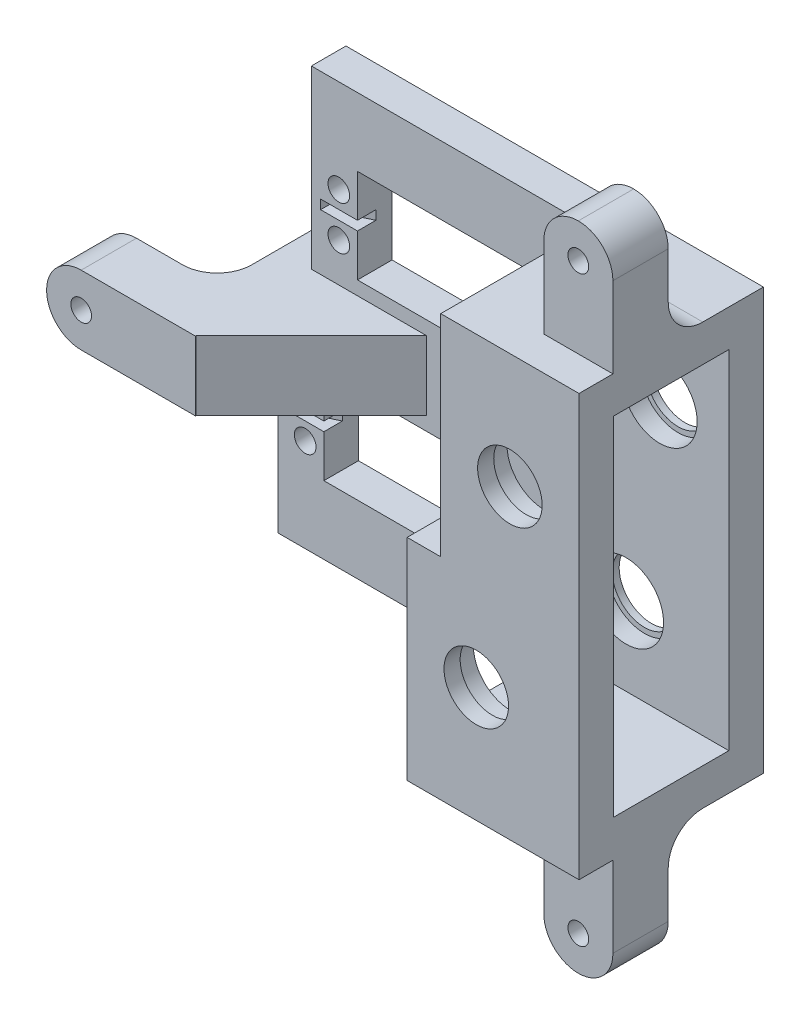
SolidWorks part; units mm, degrees
ref_plane "Front Plane" through (0, 0, 0) normal (0, 0, 1) x (1, 0, 0)
ref_plane "Top Plane" through (0, 0, 0) normal (0, 1, 0) x (1, 0, 0)
ref_plane "Right Plane" through (0, 0, 0) normal (1, 0, 0) x (0, 0, -1)
sketch "Sketch1" plane through (0, 0, 0) normal (0, 0, 1) x (1, 0, 0)
  line L0 (-15, 0) -> (22.2932, 0)
  line L5 (-15, 91.3619) -> (22.2932, 91.3619)
  line L6 (-15, 0) -> (-15, 91.3619)
  line L7 (22.2932, 0) -> (22.2932, 91.3619)
  line L8 (0, 25) -> (7.2932, 66.3619) construction
  line L9 (0, 25) -> (0, 79.2) construction
  circle A1 centre (0, 25) radius 8.125
  circle A2 centre (7.2932, 66.3619) radius 8.125
  point P4 (0, 0)
  dimension "D2" = 16.25
  dimension "D5" = 25
  dimension "D4" = 15
  dimension "D6" = 25
  dimension "D8" = 42
  dimension "D9" = 10
  dimension "D10" = 15
extrude "Boss-Extrude1" add sketch "Sketch1" along normal blind 40
ref_plane "INNER WALL" through (0, 0, 39) normal (0, 0, 1) x (1, 0, 0)
ref_plane "OUTER WALL" through (0, 0, 32.65) normal (0, 0, 1) x (1, 0, 0)
sketch "Sketch2" plane through (0, 0, 0) normal (0, 1, 0) x (1, 0, 0)
  line L1 (-15, -7.5) -> (22.2932, -7.5)
  line L2 (-15, -7.5) -> (-15, -32.5)
  line L3 (-15, -32.5) -> (22.2932, -32.5)
  line L4 (22.2932, -7.5) -> (22.2932, -32.5)
  line L6 (-15, -40) -> (-15, 0) construction
  line L7 (22.2932, -40) -> (22.2932, 0) construction
  point P9 (22.2932, -20)
  point P10 (22.2932, -20)
  dimension "D1" = 25
extrude "Cut-Extrude1" cut sketch "Sketch2" along normal through all from offset 8
sketch "Sketch10" plane through (0, 0, 40) normal (0, 0, 1) x (1, 0, 0)
  circle A0 centre (7.2932, 66.3619) radius 8.125
  circle A1 centre (0, 25) radius 10.837
  circle A2 centre (7.2932, 66.3619) radius 7
  circle A3 centre (0, 25) radius 7
  circle A4 centre (7.2932, 66.3619) radius 8.125 construction
  circle A5 centre (0, 25) radius 8.125 construction
  dimension "D2" = 14
  dimension "D4" = 14
extrude "Boss-Extrude2" add sketch "Sketch10" against normal offset from surface (3.5 mm away) 4 up to face at (-8.125, 25, 32.5)
sketch "Sketch11" plane through (0, 0, 0) normal (0, 0, -1) x (-1, 0, 0)
  circle A0 centre (-7.2932, 66.3619) radius 8.125
  circle A1 centre (-7.2932, 66.3619) radius 7
  circle A2 centre (0, 25) radius 8.125
  circle A3 centre (0, 25) radius 7
  circle A4 centre (0, 25) radius 8.125 construction
  circle A5 centre (-7.2932, 66.3619) radius 8.125 construction
  dimension "D1" = 14
  dimension "D2" = 14
extrude "Boss-Extrude3" add sketch "Sketch11" against normal offset from surface (3.5 mm away) 4 up to face at (8.125, 25, 7.5)
ref_axis "Axis1" through (0, 25, 3.5) along (0, 0, -1)
ref_plane "Plane1" through (0, 25, 0) normal (0, -1, 0) x (-1, 0, 0)
ref_axis "Axis2" through (7.2932, 66.3619, 3.5) along (0, 0, -1)
ref_plane "Plane2" through (0, 66.3619, 0) normal (0, -1, 0) x (-1, 0, 0)
sketch "Sketch12" plane through (0, 0, 0) normal (0, 0, -1) x (-1, 0, 0)
  line L0 (-20.5113, 25) -> (20.5113, 25) construction
  line L1 (15, 0) -> (75.56, 0)
  line L2 (15, 0) -> (15, 91.3619)
  line L3 (15, 91.3619) -> (68.2668, 91.3619)
  line L5 (-20.5113, 66.3619) -> (20.5113, 66.3619) construction
  line L6 (24.66, 35.2) -> (65.56, 35.2)
  line L7 (24.66, 35.2) -> (24.66, 14.8)
  line L8 (24.66, 14.8) -> (65.56, 14.8)
  line L9 (65.56, 35.2) -> (65.56, 14.8)
  line L10 (-22.2932, 91.3619) -> (15, 91.3619) construction
  line L11 (17.3668, 76.5619) -> (58.2668, 76.5619)
  line L12 (17.3668, 76.5619) -> (17.3668, 56.1619)
  line L13 (17.3668, 56.1619) -> (58.2668, 56.1619)
  line L14 (58.2668, 76.5619) -> (58.2668, 56.1619)
  line L16 (15, 0) -> (-22.2932, 0) construction
  line L17 (15, 91.3619) -> (15, 0) construction
  line L18 (68.2668, 91.3619) -> (68.2668, 45.681)
  line L19 (68.2668, 45.681) -> (75.56, 45.681)
  line L20 (75.56, 45.681) -> (75.56, 0)
  line L21 (58.2668, 56.1619) -> (58.2668, 35.2) construction
  line L22 (45.11, 35.2) -> (45.11, 14.8) construction
  line L32 (37.8168, 76.5619) -> (37.8168, 56.1619) construction
  circle A0 centre (35, 25) radius 6.6 construction
  circle A1 centre (0, 25) radius 7 construction
  circle A2 centre (27.7068, 66.3619) radius 6.6 construction
  circle A3 centre (-7.2932, 66.3619) radius 7 construction
  point P15 (45.11, 14.8)
  point P17 (58.2668, 45.681)
  point P27 (17.3668, 66.3619)
  point P34 (37.8168, 56.1619)
  point P53 (45.11, 25)
  dimension "D7" = 13.2
  dimension "D11" = 13.2
  dimension "D2" = 20.4
  dimension "D3" = 40.9
  dimension "D4" = 10.11
  dimension "D9" = 10.11
  dimension "D5" = 35
  dimension "D6" = 10
  dimension "D8" = 10
extrude "Boss-Extrude4" add sketch "Sketch12" against normal up to surface (7.5 mm away) up to face at (8.125, 25, 7.5)
sketch "Sketch13" plane through (0, 0, 0) normal (0, 0, -1) x (-1, 0, 0)
  line L0 (24.66, 35.2) -> (24.66, 14.8) construction
  line L1 (-20.5113, 25) -> (20.5113, 25) construction
  line L2 (65.56, 14.8) -> (65.56, 35.2) construction
  line L3 (17.3668, 76.5619) -> (17.3668, 56.1619) construction
  line L5 (-20.5113, 66.3619) -> (20.5113, 66.3619) construction
  line L6 (58.2668, 56.1619) -> (58.2668, 76.5619) construction
  circle A0 centre (20.61, 29.75) radius 2.3495
  circle A1 centre (20.61, 20.25) radius 2.3495
  circle A2 centre (69.61, 29.75) radius 2.3495
  circle A3 centre (69.61, 20.25) radius 2.3495
  circle A4 centre (13.3168, 71.1119) radius 2.3495
  circle A5 centre (13.3168, 61.6119) radius 2.3495
  circle A6 centre (62.3168, 71.1119) radius 2.3495
  circle A7 centre (62.3168, 61.6119) radius 2.3495
  dimension "D1" = 4.699
  dimension "D2" = 4.05
  dimension "D3" = 9.5
  dimension "D4" = 4.75
  dimension "D5" = 4.05
  dimension "D7" = 9.5
  dimension "D8" = 4.05
  dimension "D9" = 4.75
  dimension "D10" = 4.05
extrude "Cut-Extrude2" cut sketch "Sketch13" against normal up to next
sketch "Sketch22" plane through (0, 0, 7.5) normal (0, 0, 1) x (1, 0, 0)
  line L0 (-58.2668, 56.1619) -> (-58.2668, 76.5619) construction
  line L1 (-58.2668, 65.3619) -> (-66.2668, 65.3619)
  line L2 (-58.2668, 65.3619) -> (-58.2668, 67.3619)
  line L3 (-58.2668, 67.3619) -> (-66.2668, 67.3619)
  line L4 (-66.2668, 65.3619) -> (-66.2668, 67.3619)
  line L5 (-17.3668, 76.5619) -> (-17.3668, 56.1619) construction
  line L6 (-17.3668, 65.3619) -> (-9.3668, 65.3619)
  line L7 (-17.3668, 65.3619) -> (-17.3668, 67.3619)
  line L8 (-17.3668, 67.3619) -> (-9.3668, 67.3619)
  line L9 (-9.3668, 65.3619) -> (-9.3668, 67.3619)
  line L10 (-24.66, 35.2) -> (-24.66, 14.8) construction
  line L11 (-24.66, 24) -> (-16.66, 24)
  line L12 (-24.66, 24) -> (-24.66, 26)
  line L13 (-24.66, 26) -> (-16.66, 26)
  line L14 (-16.66, 24) -> (-16.66, 26)
  line L15 (-65.56, 14.8) -> (-65.56, 35.2) construction
  line L16 (-65.56, 24) -> (-73.56, 24)
  line L17 (-65.56, 24) -> (-65.56, 26)
  line L18 (-65.56, 26) -> (-73.56, 26)
  line L19 (-73.56, 24) -> (-73.56, 26)
  point P24 (-58.2668, 66.3619)
  point P25 (-66.2668, 66.3619)
  point P26 (-73.56, 25)
  point P27 (-65.56, 25)
  dimension "D1" = 2
  dimension "D2" = 8
extrude "Cut-Extrude6" cut sketch "Sketch22" against normal blind 2
sketch "Sketch14" plane through (0, 0, 7.5) normal (0, 0, 1) x (1, 0, 0)
  line L0 (22.2932, 0) -> (22.2932, 91.3619) construction
  line L1 (22.2932, 91.3619) -> (-15, 91.3619)
  line L2 (22.2932, 91.3619) -> (22.2932, 83.3619)
  line L3 (22.2932, 83.3619) -> (-15, 83.3619)
  line L4 (-15, 91.3619) -> (-15, 83.3619)
  line L5 (22.2932, 91.3619) -> (-15, 91.3619) construction
  line L6 (-15, 91.3619) -> (-15, 0) construction
  dimension "D1" = 8
extrude "Boss-Extrude5" add sketch "Sketch14" along normal up to surface (25 mm away) up to face at (-8.125, 25, 32.5)
sketch "Sketch18" plane through (0, 0, 40) normal (0, 0, 1) x (1, 0, 0)
  line L0 (7.2932, 66.3619) -> (7.2932, 25) construction
  line L1 (-15, 91.3619) -> (-7.7068, 91.3619)
  line L2 (-15, 91.3619) -> (-15, 45.681)
  line L3 (-15, 45.681) -> (-7.7068, 45.681)
  line L4 (-7.7068, 91.3619) -> (-7.7068, 45.681)
  line L5 (0, 25) -> (7.2932, 25) construction
  circle A0 centre (7.2932, 66.3619) radius 8.125 construction
  point P13 (7.2932, 45.681)
  dimension "D1" = 15
extrude "Cut-Extrude4" cut sketch "Sketch18" against normal up to surface (32.5 mm away) up to face at (-45.11, 25, 7.5)
sketch "Sketch15" plane through (0, 0, 0) normal (0, 0, -1) x (-1, 0, 0)
  circle A0 centre (0, 25) radius 11
  circle A1 centre (-7.2932, 66.3619) radius 11
  dimension "D1" = 22
extrude "Cut-Extrude3" cut sketch "Sketch15" against normal blind 2
sketch "Sketch19" plane through (0, 0, 32.65) normal (0, 0, 1) x (1, 0, 0)
  line L1 (22.2932, 91.3619) -> (7.2932, 91.3619)
  line L2 (22.2932, 91.3619) -> (22.2932, 116.3619)
  line L3 (22.2932, 116.3619) -> (7.2932, 116.3619)
  line L4 (7.2932, 91.3619) -> (7.2932, 116.3619)
  line L5 (22.2932, 0) -> (7.2932, 0)
  line L6 (22.2932, 0) -> (22.2932, -25)
  line L7 (22.2932, -25) -> (7.2932, -25)
  line L8 (7.2932, 0) -> (7.2932, -25)
  line L9 (-15, 0) -> (22.2932, 0) construction
  dimension "D1" = 15
  dimension "D2" = 25
extrude "Boss-Extrude6" add sketch "Sketch19" against normal blind 12
sketch "Sketch20" plane through (0, 0, 32.65) normal (0, 0, 1) x (1, 0, 0)
  line L0 (-15, 45.681) -> (-7.7068, 45.681) construction
  line L1 (-100.56, 38.181) -> (-68.2668, 38.181)
  line L2 (-100.56, 38.181) -> (-100.56, 53.181)
  line L3 (-100.56, 53.181) -> (-68.2668, 53.181)
  line L4 (-68.2668, 38.181) -> (-68.2668, 53.181)
  line L5 (-75.56, 0) -> (-75.56, 45.681) construction
  line L6 (-68.2668, 45.681) -> (-68.2668, 91.3619) construction
  point P4 (-68.2668, 45.681)
  dimension "D1" = 25
  dimension "D2" = 15
extrude "Boss-Extrude7" add sketch "Sketch20" against normal blind 12 separate body
sketch "Sketch21" plane through (0, 0, 20.65) normal (0, 0, -1) x (-1, 0, 0)
  line L0 (100.56, 38.181) -> (68.2668, 38.181) construction
  line L1 (68.2668, 53.181) -> (75.56, 53.181)
  line L2 (68.2668, 53.181) -> (68.2668, 38.181)
  line L3 (68.2668, 38.181) -> (75.56, 38.181)
  line L4 (75.56, 53.181) -> (75.56, 38.181)
  line L5 (75.56, 0) -> (75.56, 45.681) construction
extrude "Boss-Extrude8" add sketch "Sketch21" along normal up to surface (20.65 mm away) up to face at (-11, 25, 0)
chamfer "Chamfer2" distance 2 angle 65 4 edges at (-65.56, 25, 5.5) (-58.2668, 66.3619, 5.5) (-17.3668, 66.3619, 5.5) (-24.66, 25, 5.5) first distance on face at (-65.56, 25, 5.125) first distance on face at (-58.2668, 66.3619, 5.125) first distance on face at (-17.3668, 66.3619, 5.125) first distance on face at (-24.66, 25, 5.125)
fillet "Fillet1" radius 7.5 9 edges at (-100.56, 53.181, 26.65) (-100.56, 38.181, 26.65) (-75.56, 45.681, 20.65) (7.2932, 116.3619, 26.65) (22.2932, 116.3619, 26.65) (7.2932, -25, 26.65) (22.2932, -25, 26.65) (14.7932, 0, 20.65) (14.7932, 91.3619, 20.65)
chamfer "Chamfer1" distance 25 angle 45 1 edges at (-68.2668, 45.681, 7.5)
hole_wizard "M4 Clearance Hole1" positions "Sketch23" profile "Sketch24" hole size "M4" standard "ANSI Metric" end condition through all
sketch "Sketch23" plane through (0, 0, 20.65) normal (0, 0, -1) x (-1, 0, 0)
  point P0 (-14.7932, 108.8619)
  point P3 (93.06, 45.681)
  point P6 (-14.7932, -17.5)
sketch "Sketch24" plane through (14.7932, 108.8619, 20.65) normal (1, 0, 0) x (0, 1, 0)
  line L0 (0, 0) -> (0, 19.35)
  line L1 (0, 19.35) -> (2.25, 19.35)
  line L2 (2.25, 19.35) -> (2.25, 0.025)
  line L3 (2.25, 0.025) -> (2.275, 0)
  line L5 (2.275, 0) -> (0, 0)
  line L6 (-2.25, 0.025) -> (-2.275, 0) construction
  line L11 (0, -6.35) -> (0, 107.95) construction
  dimension "Thru Hole Dia." = 4.5
  dimension "Thru Hole Depth" = 19.35
  dimension "Near C'Sink Dia." = 4.55
  dimension "Near C'Sink Angle" = 90
equation "\"D4@Sketch13\"=\"D3@Sketch13\"/2"
equation "\"D5@Sketch12\"=\"D1@Sketch12\""
equation "\"D8@Sketch13\"=\"D2@Sketch13\""
equation "\"D9@Sketch13\"=\"D7@Sketch13\"/2"
equation "\"D10@Sketch13\"=\"D5@Sketch13\""
